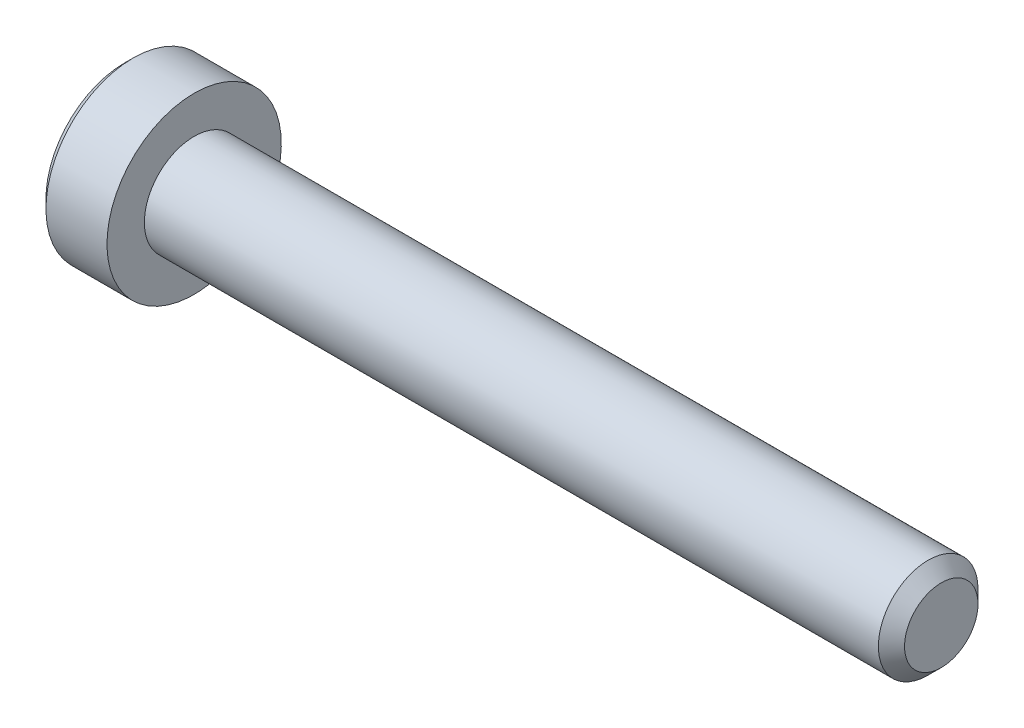
SolidWorks part; units mm, degrees
ref_plane "Front Plane" through (0, 0, 0) normal (0, 0, 1) x (1, 0, 0)
ref_plane "Top Plane" through (0, 0, 0) normal (0, 1, 0) x (1, 0, 0)
ref_plane "Right Plane" through (0, 0, 0) normal (1, 0, 0) x (0, 0, -1)
sketch "Sketch1" plane through (0, 0, 0) normal (0, 0, 1) x (1, 0, 0)
  line L0 (15, 0) -> (-15, 0) construction
  line L1 (15, 2) -> (15, -2) construction
  line L2 (-15, 3.5) -> (-15, -3.5) construction
  line L3 (-15, 3.5) -> (-17.45, 3.5) construction
  line L4 (-17.45, 3.5) -> (-17.8, 3.15) construction
  line L5 (-17.8, 3.15) -> (-17.8, -3.15) construction
  line L6 (-17.8, -3.15) -> (-17.45, -3.5) construction
  line L7 (-17.45, -3.5) -> (-15, -3.5) construction
  line L8 (1, 2) -> (1, -2) construction
  line L9 (14.9562, 2.0758) -> (15.6562, 2.0758) construction
  line L10 (15.6562, 2.0758) -> (15.3063, 1.4696) construction
  line L11 (15.3063, 1.4696) -> (14.9562, 2.0758) construction
  line L12 (15.3063, 2.0758) -> (15.3063, 2) construction
  line L13 (15.3063, 1.4696) -> (15.3063, 1.5453) construction
  line L14 (15, 2) -> (15.6125, 2) construction
  line L15 (15.2625, 1.5453) -> (15.35, 1.5453)
  line L16 (14.9781, 2.0379) -> (15.6344, 2.0379)
  line L17 (15.6344, 2.0379) -> (15.35, 1.5453)
  line L18 (15.2625, 1.5453) -> (14.9781, 2.0379)
  line L19 (-15.38, -1.25) -> (-15.38, 1.25)
  point P7 (-15.38, 0)
  point P12 (12.55, -2)
  point P24 (15.3063, 2)
  point P27 (15.3063, 1.5453)
  point P30 (15.3063, 2.0379)
  point P34 (-15.38, 0)
  dimension "D1" = 45
  dimension "Thread Size" = 4
  dimension "Length" = 30
  dimension "Head DiameterSketch1" = 7
  dimension "Head Height" = 2.8
  dimension "Hex Depth" = 2.42
  dimension "Chamfer" = 0.35
  dimension "D2" = 2.45
  dimension "Thread Pitch" = 0.7
  dimension "D3" = 0.0875
  dimension "Drive Size" = 2.5
ref_plane "Plane1" through (15, 0, 0) normal (1, 0, 0) x (0, 0, -1)
ref_plane "Plane2" through (-17.8, 0, 0) normal (1, 0, 0) x (0, 0, -1)
sketch "Sketch2" plane through (15, 0, 0) normal (1, 0, 0) x (0, 0, -1)
  circle A0 centre (0, 0) radius 2
extrude "Boss-Extrude1" add sketch "Sketch2" against normal up to vertex (14 mm away) up to point (1, 2, 0)
sketch "Sketch3" [suppressed] plane through (15, 0, 0) normal (1, 0, 0) x (0, 0, -1)
  circle A0 centre (0, 0) radius 2 construction
  circle A1 centre (0, 0) radius 2
chamfer "Chamfer1" distance 0.525 angle 45 1 edges at (15, 0, -2)
sketch "Sketch4" plane through (-17.8, 0, 0) normal (1, 0, 0) x (0, 0, -1)
  line L0 (-3.5, 0.7937) -> (3.5, 0.7937) construction
  line L1 (0, 1.4434) -> (-1.25, 0.7217)
  line L2 (-1.25, 0.7217) -> (-1.25, -0.7217)
  line L3 (-1.25, -0.7217) -> (0, -1.4434)
  line L4 (0, -1.4434) -> (1.25, -0.7217)
  line L5 (1.25, -0.7217) -> (1.25, 0.7217)
  line L6 (1.25, 0.7217) -> (0, 1.4434)
  line L7 (0, 0) -> (0, 0.7937) construction
  circle A0 centre (0, 0) radius 1.25 construction
  dimension "D1" = 7
  dimension "D2" = 0.7937
sketch "Sketch10" plane through (0, 0, 0) normal (0, 0, 1) x (1, 0, 0)
  line L0 (-15, 0) -> (2.1547, 0) construction
  line L1 (2.1547, 0) -> (1, 2)
  line L2 (1, 2) -> (-15, 2)
  line L3 (-15, 2) -> (-15, 0)
  line L4 (-15, 3.5) -> (-15, -3.5) construction
  line L5 (-15, 0) -> (2.1547, 0)
  dimension "D1" = 60
revolve "Revolve2" add sketch "Sketch10" angle 360 about L0
sketch "Sketch6" plane through (0, 0, 0) normal (0, 0, 1) x (1, 0, 0)
  line L0 (-17.45, 3.5) -> (-17.8, 3.15) construction
  line L1 (-15, 3.5) -> (-17.45, 3.5) construction
  line L2 (-15, 3.5) -> (-15, -3.5) construction
  line L3 (-17.8, 3.15) -> (-17.8, -3.15) construction
  line L4 (-17.45, 3.5) -> (-17.8, 3.15)
  line L5 (-15, 3.5) -> (-17.45, 3.5)
  line L6 (-15, 3.5) -> (-15, 0)
  line L7 (-17.8, 3.15) -> (-17.8, 0)
  line L8 (-15, 0) -> (-17.8, 0) construction
  line L9 (-15, 0) -> (-17.8, 0)
revolve "Revolve1" add sketch "Sketch6" angle 360 about L8
extrude "Cut-Extrude1" cut sketch "Sketch4" along normal up to vertex (2.42 mm away) up to point (-15.38, 0, 0)
sketch "Sketch8" plane through (-17.8, 0, 0) normal (-1, 0, 0) x (0, 0, 1)
  circle A1 centre (0, 0) radius 1.4434
extrude "Cut-Extrude2" cut sketch "Sketch8" against normal through all draft 45
curve "Helix/Spiral1" [suppressed] pitch 0.7 height 14.7 turns 21 parameters "Pitch"=0.7
ref_plane "Plane3" [suppressed] through (1, 2, 0) normal (-1, 0, 0) x (0, 0, 1)
split "Split1" [suppressed] bodies to split 105
sketch "Sketch5" [suppressed] plane through (0, 0, 0) normal (0, 0, 1) x (1, 0, 0)
  line L0 (14.9781, 2.0379) -> (15.6344, 2.0379) construction
  line L1 (15.2625, 1.5453) -> (14.9781, 2.0379) construction
  line L2 (15.2625, 1.5453) -> (15.35, 1.5453) construction
  line L3 (15.6344, 2.0379) -> (15.35, 1.5453) construction
  line L4 (14.9781, 2.0379) -> (15.6344, 2.0379)
  line L5 (15.2625, 1.5453) -> (14.9781, 2.0379)
  line L6 (15.2625, 1.5453) -> (15.35, 1.5453)
  line L7 (15.6344, 2.0379) -> (15.35, 1.5453)
sweep "Cut-Sweep1" [suppressed] cut profiles "Sketch5" path "Helix/Spiral1"
sketch "Sketch11" [suppressed] plane through (1, 2, 0) normal (-1, 0, 0) x (0, 0, 1)
  line L0 (0, 0) -> (0, -4) construction
  circle A0 centre (0, -2) radius 2
extrude "Boss-Extrude2" [suppressed] add sketch "Sketch11" against normal blind 10 draft 20
equation "\"D3@Helix/Spiral1\" = \"Minimum Thread Length@Sketch1\" + \"Pitch@Helix/Spiral1\""
equation "\"D1@Chamfer1\" = \"Pitch@Helix/Spiral1\"*.75"
equation "\"D2@Sketch1\"=\"Pitch@Helix/Spiral1\"*3.5"
equation "\"D1@Sketch4\" = \"Head DiameterSketch1@Sketch1\""
equation "\"Chamfer@Sketch1\" = \"Head Height@Sketch1\"/8"
equation "\"D3@Sketch1\"=\"Thread Pitch@Sketch1\"/8"
equation "\"Pitch@Helix/Spiral1\"=\"Thread Pitch@Sketch1\""
